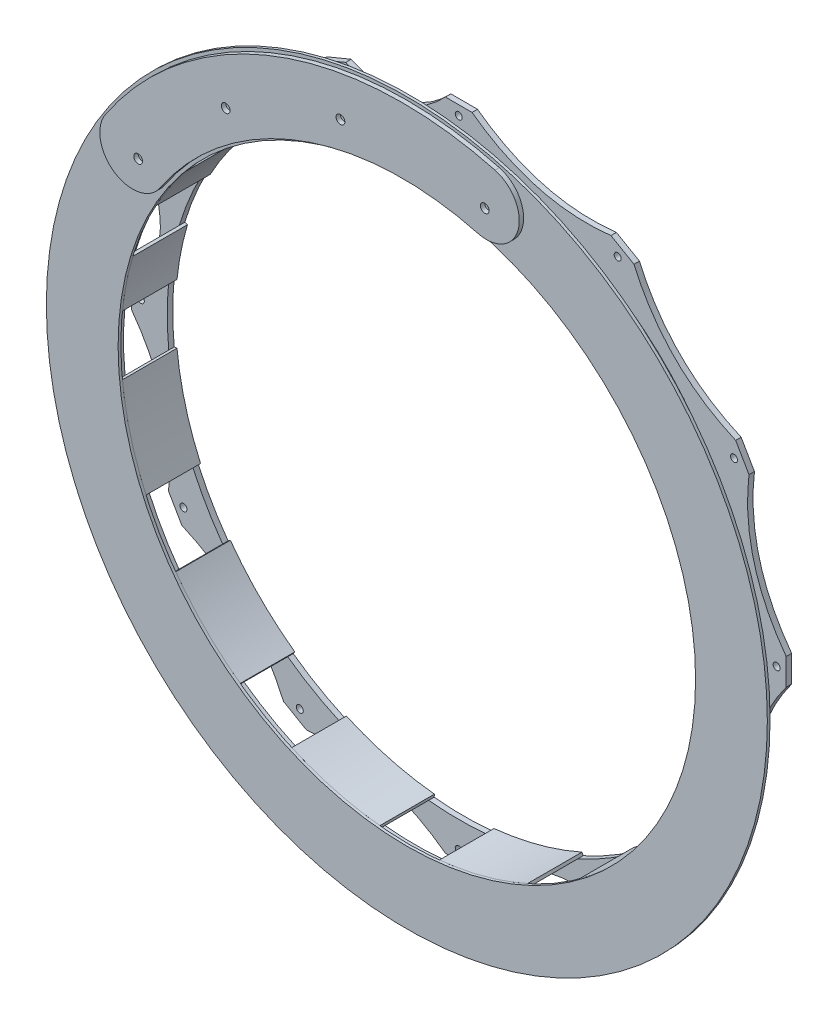
SolidWorks part; units mm, degrees
material "Maple"
ref_plane "Wasteboard" through (0, 0, 0) normal (0, 0, 1) x (1, 0, 0)
ref_plane "Left-Right" through (0, 0, 0) normal (0, 1, 0) x (1, 0, 0)
ref_plane "Front-Back" through (0, 0, 0) normal (1, 0, 0) x (0, 0, -1)
sketch "Sketch2" plane through (0, 0, 0) normal (0, 0, 1) x (1, 0, 0)
  line L0 (0, 0) -> (0, 50000) construction
  circle A0 centre (0, 0) radius 192.8812 construction
  circle A1 centre (0, 0) radius 209.55 construction
  circle A2 centre (0, 0) radius 172.72 construction
  circle A3 centre (0, 0) radius 252.73 construction
  circle A4 centre (0, 0) radius 184.785 construction
  circle A5 centre (0, 0) radius 190.5
  circle A6 centre (0, 0) radius 169.4688
  circle A7 centre (0, 0) radius 194.31 construction
  circle A8 centre (0, 184.785) radius 9.525 construction
  point P14 (0, 172.72)
  point P15 (0, 169.4688)
  point P16 (0, 175.26)
  dimension "D1" = 385.7625
  dimension "D2" = 419.1
  dimension "D3" = 2.54
  dimension "D4" = 505.46
  dimension "D5" = 369.57
  dimension "D6" = 381
  dimension "D7" = 3.2512
  dimension "D8" = 388.62
  dimension "D9" = 19.05
sketch "Sketch4" plane through (0, 0, 0) normal (0, 0, 1) x (1, 0, 0)
  line L0 (92.3925, 160.0285) -> (0, 184.785) construction
  line L1 (46.1963, 172.4068) -> (-12894.756, -48123.8846) construction
  line L2 (-7.7353, 190.3429) -> (7.7353, 190.3429)
  line L6 (-160.9741, -101.8704) -> (-168.7094, -88.4724)
  line L7 (-88.4724, -168.7094) -> (-101.8704, -160.9741)
  line L8 (7.7353, -190.3429) -> (-7.7353, -190.3429)
  line L9 (101.8704, -160.9741) -> (88.4724, -168.7094)
  line L10 (168.7094, -88.4724) -> (160.9741, -101.8704)
  line L11 (190.3429, 7.7353) -> (190.3429, -7.7353)
  line L12 (160.9741, 101.8704) -> (168.7094, 88.4724)
  line L13 (88.4724, 168.7094) -> (101.8704, 160.9741)
  line L14 (-101.8704, 160.9741) -> (-88.4724, 168.7094) [skipped]
  line L15 (-168.7094, 88.4724) -> (-160.9741, 101.8704) [skipped]
  line L16 (-79.9876, 172.8937) -> (-65.6945, 178.8141)
  line L17 (-70.7142, 170.7191) -> (0, 184.785) construction
  line L18 (-35.3571, 177.752) -> (9719.159, -48861.512) construction
  line L19 (-140.0625, 129.123) -> (-129.123, 140.0625)
  line L20 (-178.8141, 65.6945) -> (-172.8937, 79.9876)
  line L21 (-190.3429, -7.7353) -> (-190.3429, 7.7353)
  line L23 (-172.8937, -79.9876) -> (-178.8141, -65.6945) [skipped]
  line L24 (-190.3429, -7.7353) -> (-190.3429, 7.7353) [skipped]
  circle A0 centre (0, 184.785) radius 3.175 construction
  circle A1 centre (0, 184.785) radius 9.525 construction
  circle A2 centre (0, 184.785) radius 9.525 construction
  circle A3 centre (0, 0) radius 177.6413 construction
  circle A4 centre (0, 0) radius 190.5 construction
  circle A5 centre (0, 0) radius 184.785 construction
  circle A6 centre (0, 0) radius 169.4688 construction
  circle A7 centre (0, 0) radius 169.4688
  circle A8 centre (92.3925, 160.0285) radius 9.525 construction
  circle A9 centre (0, 0) radius 192.8812 construction
  circle A10 centre (0, 184.785) radius 2.032
  circle A14 centre (-160.0285, -92.3925) radius 2.032
  circle A15 centre (-92.3925, -160.0285) radius 2.032
  circle A16 centre (0, -184.785) radius 2.032
  circle A17 centre (92.3925, -160.0285) radius 2.032
  circle A18 centre (160.0285, -92.3925) radius 2.032
  circle A19 centre (184.785, 0) radius 2.032
  circle A20 centre (160.0285, 92.3925) radius 2.032
  circle A21 centre (92.3925, 160.0285) radius 2.032
  circle A22 centre (-160.0285, 92.3925) radius 2.032 [skipped]
  circle A23 centre (-92.3925, 160.0285) radius 2.032 [skipped]
  circle A24 centre (-70.7142, 170.7191) radius 9.525 construction
  circle A25 centre (-130.6627, 130.6627) radius 9.525 construction
  circle A26 centre (-170.7191, 70.7142) radius 9.525 construction
  circle A27 centre (-184.785, 0) radius 9.525 construction
  circle A28 centre (-70.7142, 170.7191) radius 2.032
  circle A29 centre (-130.6627, 130.6627) radius 2.032
  circle A30 centre (-170.7191, 70.7142) radius 2.032
  circle A31 centre (-184.785, 0) radius 2.032
  circle A32 centre (-184.785, 0) radius 2.032 [skipped]
  spline S0 degree 2 poles (7.7353, 190.3429) (43.85, 163.6504) (88.4724, 168.7094) knots 0 0 0 1 1 1
  spline S1 degree 2 poles (-65.6945, 178.8141) (-32.5972, 163.8774) (-7.7353, 190.3429) knots 0 0 0 1 1 1
  spline S2 degree 2 poles (-129.123, 140.0625) (-92.8291, 138.9285) (-79.9876, 172.8937) knots 0 0 0 1 1 1
  spline S3 degree 2 poles (-172.8937, 79.9876) (-138.9285, 92.8291) (-140.0625, 129.123) knots 0 0 0 1 1 1
  spline S4 degree 2 poles (-168.7094, -88.4724) (-163.6504, -43.85) (-190.3429, -7.7353) knots 0 0 0 1 1 1
  spline S5 degree 2 poles (-101.8704, -160.9741) (-119.8004, -119.8004) (-160.9741, -101.8704) knots 0 0 0 1 1 1
  spline S6 degree 2 poles (-7.7353, -190.3429) (-43.85, -163.6504) (-88.4724, -168.7094) knots 0 0 0 1 1 1
  spline S7 degree 2 poles (88.4724, -168.7094) (43.85, -163.6504) (7.7353, -190.3429) knots 0 0 0 1 1 1
  spline S8 degree 2 poles (160.9741, -101.8704) (119.8004, -119.8004) (101.8704, -160.9741) knots 0 0 0 1 1 1
  spline S9 degree 2 poles (190.3429, -7.7353) (163.6504, -43.85) (168.7094, -88.4724) knots 0 0 0 1 1 1
  spline S10 degree 2 poles (168.7094, 88.4724) (163.6504, 43.85) (190.3429, 7.7353) knots 0 0 0 1 1 1
  spline S11 degree 2 poles (101.8704, 160.9741) (119.8004, 119.8004) (160.9741, 101.8704) knots 0 0 0 1 1 1
  spline S12 degree 2 poles (-190.3429, 7.7353) (-163.8774, 32.5972) (-178.8141, 65.6945) knots 0 0 0 1 1 1
  point P6 (0, 0)
  point P18 (0, 0)
  point P19 (0, 0)
  point P21 (0, 0)
  point P24 (45.9769, 171.5883)
  point P29 (46.1963, 172.4068)
  point P31 (-7.7353, 190.3429)
  point P33 (-79.9876, 172.8937)
  point P34 (-65.6945, 178.8141)
  point P45 (0, 0)
  point P48 (-34.6561, 174.2279)
  point P103 (0, 0)
  point P112 (-35.3571, 177.752)
  point P123 (0, 0)
  point P126 (0, 0)
  dimension "D1" = 6.35
  dimension "D2" = 19.05
  dimension "D3" = 15.24
  dimension "D6" = 4.064
  dimension "D7" = 12
  dimension "D4" = 2
  dimension "D5" = 2
  dimension "D8" = 5
  dimension "D9" = 5
extrude "Boss-Extrude1" add sketch "Sketch4" along normal blind 3.175
ref_plane "Plane1" through (0, 0, 28.575) normal (0, 0, 1) x (1, 0, 0)
sketch "Sketch5" plane through (0, 0, 28.575) normal (0, 0, 1) x (1, 0, 0)
  line L13 (-129.123, 140.0625) -> (-140.0625, 129.123)
  line L14 (-65.6945, 178.8141) -> (-79.9876, 172.8937)
  line L15 (7.7353, 190.3429) -> (-7.7353, 190.3429)
  line L16 (101.8704, 160.9741) -> (88.4724, 168.7094)
  line L17 (168.7094, 88.4724) -> (160.9741, 101.8704)
  line L18 (190.3429, -7.7353) -> (190.3429, 7.7353)
  line L19 (160.9741, -101.8704) -> (168.7094, -88.4724)
  line L20 (88.4724, -168.7094) -> (101.8704, -160.9741)
  line L21 (-7.7353, -190.3429) -> (7.7353, -190.3429)
  line L22 (-101.8704, -160.9741) -> (-88.4724, -168.7094)
  line L23 (-168.7094, -88.4724) -> (-160.9741, -101.8704)
  line L24 (-190.3429, 7.7353) -> (-190.3429, -7.7353)
  line L25 (-172.8937, 79.9876) -> (-178.8141, 65.6945)
  line L26 (-129.123, 140.0625) -> (-140.0625, 129.123)
  line L27 (-65.6945, 178.8141) -> (-79.9876, 172.8937)
  line L28 (7.7353, 190.3429) -> (-7.7353, 190.3429)
  line L29 (101.8704, 160.9741) -> (88.4724, 168.7094)
  line L30 (168.7094, 88.4724) -> (160.9741, 101.8704)
  line L31 (190.3429, -7.7353) -> (190.3429, 7.7353)
  line L32 (160.9741, -101.8704) -> (168.7094, -88.4724)
  line L33 (88.4724, -168.7094) -> (101.8704, -160.9741)
  line L34 (-7.7353, -190.3429) -> (7.7353, -190.3429)
  line L35 (-101.8704, -160.9741) -> (-88.4724, -168.7094)
  line L36 (-168.7094, -88.4724) -> (-160.9741, -101.8704)
  line L37 (-190.3429, 7.7353) -> (-190.3429, -7.7353)
  line L38 (-172.8937, 79.9876) -> (-178.8141, 65.6945)
  circle A1 centre (0, 0) radius 169.4688
  circle A2 centre (0, 0) radius 169.4688
  circle A3 centre (0, 184.785) radius 2.032
  circle A4 centre (0, 184.785) radius 2.032
  circle A5 centre (-160.0285, -92.3925) radius 2.032
  circle A6 centre (-160.0285, -92.3925) radius 2.032
  circle A7 centre (-70.7142, 170.7191) radius 2.032
  circle A8 centre (-70.7142, 170.7191) radius 2.032
  circle A9 centre (92.3925, -160.0285) radius 2.032
  circle A10 centre (92.3925, -160.0285) radius 2.032
  circle A11 centre (0, -184.785) radius 2.032
  circle A12 centre (0, -184.785) radius 2.032
  circle A13 centre (-92.3925, -160.0285) radius 2.032
  circle A14 centre (-92.3925, -160.0285) radius 2.032
  circle A15 centre (184.785, 0) radius 2.032
  circle A16 centre (184.785, 0) radius 2.032
  circle A17 centre (160.0285, -92.3925) radius 2.032
  circle A18 centre (160.0285, -92.3925) radius 2.032
  circle A19 centre (92.3925, 160.0285) radius 2.032
  circle A20 centre (92.3925, 160.0285) radius 2.032
  circle A21 centre (160.0285, 92.3925) radius 2.032
  circle A22 centre (160.0285, 92.3925) radius 2.032
  circle A23 centre (-184.785, 0) radius 2.032
  circle A24 centre (-184.785, 0) radius 2.032
  circle A25 centre (-170.7191, 70.7142) radius 2.032
  circle A26 centre (-170.7191, 70.7142) radius 2.032
  circle A27 centre (-130.6627, 130.6627) radius 2.032
  circle A28 centre (-130.6627, 130.6627) radius 2.032
  parabola Q13 (-140.0625, 129.123) -> (-172.8937, 79.9876) focus (-164.8995, 110.1823) apex (-147.7033, 98.6922)
  parabola Q14 (-79.9876, 172.8937) -> (-129.123, 140.0625) focus (-110.1823, 164.8995) apex (-98.6922, 147.7033)
  parabola Q15 (-7.7353, 190.3429) -> (-65.6945, 178.8141) focus (-38.6909, 194.5123) apex (-34.6561, 174.2279)
  parabola Q16 (88.4724, 168.7094) -> (7.7353, 190.3429) focus (59.7292, 222.9123) apex (45.9769, 171.5883)
  parabola Q17 (160.9741, 101.8704) -> (101.8704, 160.9741) focus (163.1831, 163.1831) apex (125.6113, 125.6113)
  parabola Q18 (190.3429, 7.7353) -> (168.7094, 88.4724) focus (222.9123, 59.7292) apex (171.5883, 45.9769)
  parabola Q19 (168.7094, -88.4724) -> (190.3429, -7.7353) focus (222.9123, -59.7292) apex (171.5883, -45.9769)
  parabola Q20 (101.8704, -160.9741) -> (160.9741, -101.8704) focus (163.1831, -163.1831) apex (125.6113, -125.6113)
  parabola Q21 (7.7353, -190.3429) -> (88.4724, -168.7094) focus (59.7292, -222.9123) apex (45.9769, -171.5883)
  parabola Q22 (-88.4724, -168.7094) -> (-7.7353, -190.3429) focus (-59.7292, -222.9123) apex (-45.9769, -171.5883)
  parabola Q23 (-160.9741, -101.8704) -> (-101.8704, -160.9741) focus (-163.1831, -163.1831) apex (-125.6113, -125.6113)
  parabola Q24 (-190.3429, -7.7353) -> (-168.7094, -88.4724) focus (-222.9123, -59.7292) apex (-171.5883, -45.9769)
  parabola Q25 (-178.8141, 65.6945) -> (-190.3429, 7.7353) focus (-194.5123, 38.6909) apex (-174.2279, 34.6561)
  parabola Q26 (-140.0625, 129.123) -> (-172.8937, 79.9876) focus (-164.8995, 110.1823) apex (-147.7033, 98.6922)
  parabola Q27 (-79.9876, 172.8937) -> (-129.123, 140.0625) focus (-110.1823, 164.8995) apex (-98.6922, 147.7033)
  parabola Q28 (-7.7353, 190.3429) -> (-65.6945, 178.8141) focus (-38.6909, 194.5123) apex (-34.6561, 174.2279)
  parabola Q29 (88.4724, 168.7094) -> (7.7353, 190.3429) focus (59.7292, 222.9123) apex (45.9769, 171.5883)
  parabola Q30 (160.9741, 101.8704) -> (101.8704, 160.9741) focus (163.1831, 163.1831) apex (125.6113, 125.6113)
  parabola Q31 (190.3429, 7.7353) -> (168.7094, 88.4724) focus (222.9123, 59.7292) apex (171.5883, 45.9769)
  parabola Q32 (168.7094, -88.4724) -> (190.3429, -7.7353) focus (222.9123, -59.7292) apex (171.5883, -45.9769)
  parabola Q33 (101.8704, -160.9741) -> (160.9741, -101.8704) focus (163.1831, -163.1831) apex (125.6113, -125.6113)
  parabola Q34 (7.7353, -190.3429) -> (88.4724, -168.7094) focus (59.7292, -222.9123) apex (45.9769, -171.5883)
  parabola Q35 (-88.4724, -168.7094) -> (-7.7353, -190.3429) focus (-59.7292, -222.9123) apex (-45.9769, -171.5883)
  parabola Q36 (-160.9741, -101.8704) -> (-101.8704, -160.9741) focus (-163.1831, -163.1831) apex (-125.6113, -125.6113)
  parabola Q37 (-190.3429, -7.7353) -> (-168.7094, -88.4724) focus (-222.9123, -59.7292) apex (-171.5883, -45.9769)
  parabola Q38 (-178.8141, 65.6945) -> (-190.3429, 7.7353) focus (-194.5123, 38.6909) apex (-174.2279, 34.6561)
  dimension "D1" = 0
  dimension "D2" = 0
  dimension "D3" = 0
  dimension "D4" = 0
  dimension "D5" = 0
  dimension "D6" = 0
  dimension "D7" = 0
  dimension "D8" = 0
  dimension "D9" = 0
  dimension "D10" = 0
  dimension "D11" = 0
  dimension "D12" = 0
  dimension "D13" = 0
  dimension "D14" = 0
  dimension "D15" = 0
extrude "Boss-Extrude2" add sketch "Sketch5" along normal blind 3.175 separate body
sketch "Sketch6" plane through (0, 0, 31.75) normal (0, 0, 1) x (1, 0, 0)
  line L0 (0, 0) -> (5154.6392, 49733.5872) construction
  line L1 (0, 0) -> (20402.7451, 45647.8695) construction
  line L2 (17.471, 168.5658) -> (17.3034, 166.9489)
  line L3 (68.4892, 153.2337) -> (69.1526, 154.7178)
  line L4 (99.4133, 137.2468) -> (98.4596, 135.9303)
  line L5 (135.9303, 98.4596) -> (137.2468, 99.4133)
  line L6 (154.7178, 69.1526) -> (153.2337, 68.4892)
  line L7 (166.9489, 17.3034) -> (168.5658, 17.471)
  line L8 (168.5658, -17.471) -> (166.9489, -17.3034)
  line L9 (153.2337, -68.4892) -> (154.7178, -69.1526)
  line L10 (137.2468, -99.4133) -> (135.9303, -98.4596)
  line L11 (98.4596, -135.9303) -> (99.4133, -137.2468)
  line L12 (69.1526, -154.7178) -> (68.4892, -153.2337)
  line L39 (17.3034, -166.9489) -> (17.471, -168.5658)
  line L40 (-17.471, -168.5658) -> (-17.3034, -166.9489)
  line L41 (-68.4892, -153.2337) -> (-69.1526, -154.7178)
  line L42 (-99.4133, -137.2468) -> (-98.4596, -135.9303)
  line L43 (-135.9303, -98.4596) -> (-137.2468, -99.4133)
  line L44 (-154.7178, -69.1526) -> (-153.2337, -68.4892)
  line L45 (-166.9489, -17.3034) -> (-168.5658, -17.471)
  line L46 (0, 0) -> (68.4892, 153.2337) construction
  line L47 (0, 0) -> (135.9303, 98.4596) construction
  line L48 (0, 0) -> (-5154.6392, 49733.5872) construction
  line L49 (0, 0) -> (-14269.9542, 47920.4383) construction
  line L50 (-47.9023, 160.8624) -> (-48.3662, 162.4204)
  line L51 (-17.3034, 166.9489) -> (-17.471, 168.5658)
  line L52 (-105.8153, 130.2861) -> (-106.8402, 131.5479)
  line L53 (-79.8749, 147.6189) -> (-80.6485, 149.0487)
  line L54 (-147.6189, 79.8749) -> (-149.0487, 80.6485)
  line L55 (-130.2861, 105.8153) -> (-131.5479, 106.8402)
  line L56 (-166.9489, 17.3034) -> (-168.5658, 17.471)
  line L57 (-160.8624, 47.9023) -> (-162.4204, 48.3662)
  line L58 (0, 0) -> (-17.3034, 166.9489) construction
  line L59 (0, 0) -> (-79.8749, 147.6189) construction
  circle A0 centre (92.3925, 160.0285) radius 2.032 construction
  arc A1 (17.471, 168.5658) -> (69.1526, 154.7178) centre (0, 0) cw
  circle A2 centre (0, 0) radius 169.4688 construction
  arc A3 (17.3034, 166.9489) -> (68.4892, 153.2337) centre (0, 0) cw
  arc A4 (99.4133, 137.2468) -> (137.2468, 99.4133) centre (0, 0) cw
  arc A5 (98.4596, 135.9303) -> (135.9303, 98.4596) centre (0, 0) cw
  arc A6 (154.7178, 69.1526) -> (168.5658, 17.471) centre (0, 0) cw
  arc A7 (153.2337, 68.4892) -> (166.9489, 17.3034) centre (0, 0) cw
  arc A8 (168.5658, -17.471) -> (154.7178, -69.1526) centre (0, 0) cw
  arc A9 (166.9489, -17.3034) -> (153.2337, -68.4892) centre (0, 0) cw
  arc A10 (137.2468, -99.4133) -> (99.4133, -137.2468) centre (0, 0) cw
  arc A11 (135.9303, -98.4596) -> (98.4596, -135.9303) centre (0, 0) cw
  arc A12 (69.1526, -154.7178) -> (17.471, -168.5658) centre (0, 0) cw
  arc A13 (68.4892, -153.2337) -> (17.3034, -166.9489) centre (0, 0) cw
  arc A14 (-17.471, -168.5658) -> (-69.1526, -154.7178) centre (0, 0) cw
  arc A15 (-17.3034, -166.9489) -> (-68.4892, -153.2337) centre (0, 0) cw
  arc A16 (-99.4133, -137.2468) -> (-137.2468, -99.4133) centre (0, 0) cw
  arc A17 (-98.4596, -135.9303) -> (-135.9303, -98.4596) centre (0, 0) cw
  arc A18 (-154.7178, -69.1526) -> (-168.5658, -17.471) centre (0, 0) cw
  arc A19 (-153.2337, -68.4892) -> (-166.9489, -17.3034) centre (0, 0) cw
  circle A20 centre (-70.7142, 170.7191) radius 2.032 construction
  arc A21 (-48.3662, 162.4204) -> (-17.471, 168.5658) centre (0, 0) cw
  arc A22 (-47.9023, 160.8624) -> (-17.3034, 166.9489) centre (0, 0) cw
  arc A23 (-106.8402, 131.5479) -> (-80.6485, 149.0487) centre (0, 0) cw
  arc A24 (-105.8153, 130.2861) -> (-79.8749, 147.6189) centre (0, 0) cw
  arc A25 (-149.0487, 80.6485) -> (-131.5479, 106.8402) centre (0, 0) cw
  arc A26 (-147.6189, 79.8749) -> (-130.2861, 105.8153) centre (0, 0) cw
  arc A27 (-168.5658, 17.471) -> (-162.4204, 48.3662) centre (0, 0) cw
  arc A28 (-166.9489, 17.3034) -> (-160.8624, 47.9023) centre (0, 0) cw
  dimension "D3" = 19.05
  dimension "D7" = 19.05
  dimension "D2" = 19.05
  dimension "D4" = 1.6256
  dimension "D6" = 30
  dimension "D8" = 19.05
  dimension "D9" = 1.6256
  dimension "D11" = 22.5
  dimension "D5" = 9
  dimension "D10" = 4
extrude "Boss-Extrude3" add sketch "Sketch6" against normal through all
sketch "Sketch7" plane through (0, 0, 31.75) normal (0, 0, 1) x (1, 0, 0)
  circle A0 centre (0, 0) radius 167.8432
  circle A1 centre (0, 0) radius 209.55
  arc A2 (-166.9489, -17.3034) -> (-153.2337, -68.4892) centre (0, 0) ccw construction
  circle A5 centre (0, 0) radius 209.55 construction
  dimension "D1" = 41.7068
extrude "Boss-Extrude4" add sketch "Sketch7" along normal blind 1.5875 separate body
sketch "Sketch8" plane through (0, 0, 33.3375) normal (0, 0, 1) x (1, 0, 0)
  line L0 (27596.442, 41627.2074) -> (-27909.1744, -41442.8179) construction
  line L1 (-159.6471, 106.6728) -> (-517.5318, -428.9395) construction
  line L2 (-130.6627, 130.6627) -> (-170.7191, 70.7142) construction
  line L3 (-130.6627, 130.6627) -> (-156.9608, 104.8779) construction
  line L4 (-156.9608, 104.8779) -> (-170.7191, 70.7142) construction
  line L5 (-156.9608, 104.8779) -> (-159.6471, 106.6728) construction
  line L6 (-159.6471, 106.6728) -> (-341.4213, -256.8091) construction
  line L7 (-341.4213, -256.8091) -> (-383.66, -228.5861) construction
  line L8 (0, 184.785) -> (92.3925, 160.0285) construction
  line L9 (48.8323, 182.2448) -> (46.1963, 172.4068) construction
  line L10 (-130.6627, 130.6627) -> (-170.7191, 70.7142) construction
  line L11 (-130.6627, 130.6627) -> (-109.2149, 116.3318) construction
  line L12 (-109.2149, 116.3318) -> (-149.2713, 56.3832) construction
  line L13 (-149.2713, 56.3832) -> (-170.7191, 70.7142) construction
  line L14 (-129.2431, 86.3575) -> (-156.8765, 104.8215) construction
  line L15 (0, 209.55) -> (0, 167.7974) construction
  line L16 (0, -200000) -> (0, 250000) construction
  line L20 (-39053.4215, 196334.8081) -> (48737.2234, -245018.5681) construction
  circle A0 centre (-170.7191, 70.7142) radius 2.032 construction
  circle A1 centre (-130.6627, 130.6627) radius 2.032 construction
  circle A2 centre (-170.7191, 70.7142) radius 2.032 construction
  circle A3 centre (-130.6627, 130.6627) radius 2.032 construction
  circle A4 centre (0, 0) radius 190.5 construction
  circle A5 centre (0, 0) radius 209.55 construction
  circle A6 centre (0, 0) radius 184.785 construction
  arc A7 (48.8323, 182.2448) -> (-156.8765, 104.8215) centre (0, 0) ccw construction
  arc A8 (53.7629, 200.6457) -> (-172.716, 115.4051) centre (0, 0) ccw
  arc A9 (43.9018, 163.8439) -> (-141.037, 94.2379) centre (0, 0) ccw
  arc A10 (53.7629, 200.6457) -> (43.9018, 163.8439) centre (48.8323, 182.2448) cw
  arc A11 (-141.037, 94.2379) -> (-172.716, 115.4051) centre (-156.8765, 104.8215) cw
  circle A13 centre (47.8259, 178.4886) radius 2.54
  circle A14 centre (-153.6431, 102.661) radius 2.54
  circle A15 centre (-36.0498, 181.2344) radius 2.54
  circle A16 centre (-102.7427, 153.5885) radius 2.54
  point P30 (-153.6431, 102.661)
  point P45 (47.8259, 178.4886)
  dimension "D4" = 41.7526
  dimension "D5" = 19.05
  dimension "D7" = 5.08
  dimension "D8" = 5.08
  dimension "D9" = 5.08
  dimension "D10" = 5.08
  dimension "D1" = 36.83
  dimension "D2" = 50.8
  dimension "D3" = 406.4
  dimension "D11" = 36.322
  dimension "D6" = 19.05
extrude "Boss-Extrude5" add sketch "Sketch8" along normal blind 2.54 separate body contours A11 A9 A10 A8 A16 A15 A14 A13 region at (-61.3297, 163.0178, 33.3375)
